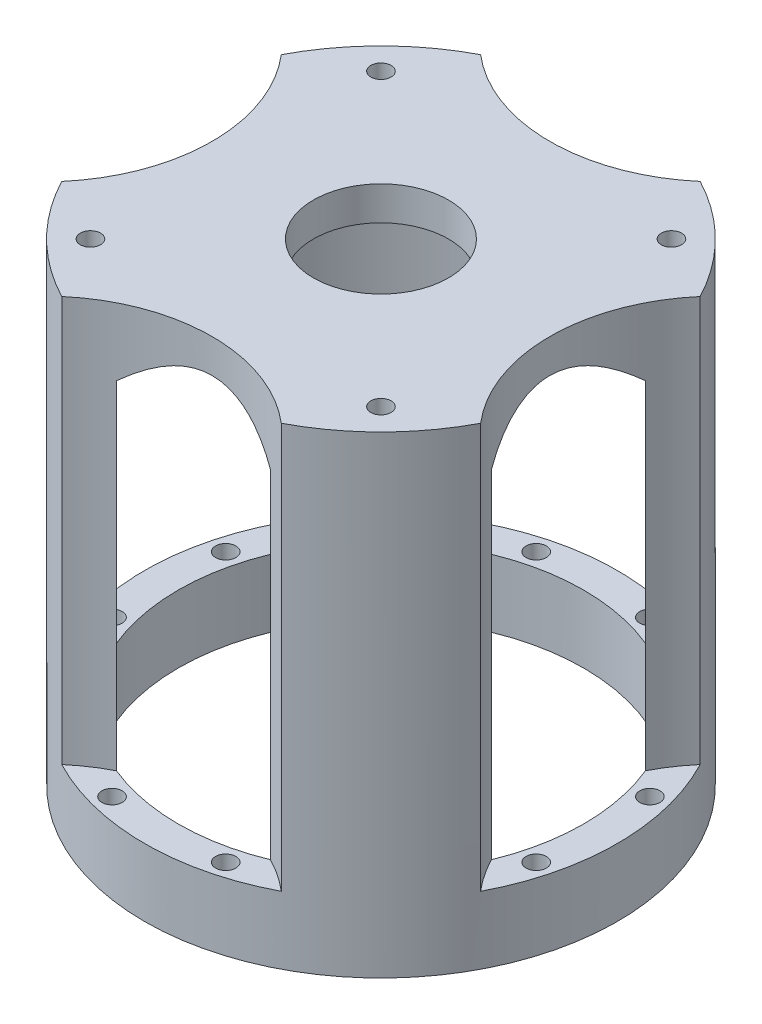
SolidWorks part; units mm, degrees
ref_plane "Front Plane" through (0, 0, 0) normal (0, 0, 1) x (1, 0, 0)
ref_plane "Top Plane" through (0, 0, 0) normal (0, 1, 0) x (1, 0, 0)
ref_plane "Right Plane" through (0, 0, 0) normal (1, 0, 0) x (0, 0, -1)
sketch "Sketch1" plane through (0, 0, 0) normal (0, 1, 0) x (1, 0, 0)
  line L0 (-8.4116, 31.3926) -> (0, 0) construction
  line L5 (-35, -35) -> (35, 35) construction
  line L6 (-35, 35) -> (35, -35) construction
  line L7 (0, 0) -> (8.6813, 0) construction
  circle A0 centre (0, 0) radius 35
  circle A1 centre (0, 0) radius 30
  circle A2 centre (0, 0) radius 32.5 construction
  circle A3 centre (-8.4116, 31.3926) radius 1.5
  circle A4 centre (8.4116, 31.3926) radius 1.5
  circle A6 centre (31.3926, 8.4116) radius 1.5
  circle A7 centre (31.3926, -8.4116) radius 1.5
  circle A9 centre (8.4116, -31.3926) radius 1.5
  circle A10 centre (-8.4116, -31.3926) radius 1.5
  circle A12 centre (-31.3926, -8.4116) radius 1.5
  circle A13 centre (-31.3926, 8.4116) radius 1.5
  circle A15 centre (22.981, -22.981) radius 1.5 [skipped]
  circle A16 centre (22.981, 22.981) radius 1.5 [skipped]
  circle A17 centre (-22.981, 22.981) radius 1.5 [skipped]
  circle A18 centre (-22.981, -22.981) radius 1.5 [skipped]
  point P35 (0, 0)
  dimension "D1" = 70
  dimension "D2" = 60
  dimension "D3" = 65
  dimension "D4" = 3
  dimension "D6" = 105
  dimension "D5" = 12
extrude "Boss-Extrude1" add sketch "Sketch1" along normal blind 65
sketch "Sketch2" plane through (0, 65, 0) normal (0, 1, 0) x (1, 0, 0)
  line L0 (-8.4116, 31.3926) -> (0, 0) construction
  line L7 (-21.5, -21.5) -> (21.5, -21.5) construction
  line L8 (-21.5, -21.5) -> (-21.5, 21.5) construction
  line L9 (-21.5, 21.5) -> (21.5, 21.5) construction
  line L10 (21.5, -21.5) -> (21.5, 21.5) construction
  line L11 (-21.5, -21.5) -> (21.5, 21.5) construction
  line L12 (-21.5, 21.5) -> (21.5, -21.5) construction
  line L13 (0, 0) -> (15.336, 0) construction
  circle A0 centre (0, 0) radius 32.5 construction
  circle A1 centre (-8.4116, 31.3926) radius 1.5
  circle A2 centre (8.4116, 31.3926) radius 1.5
  circle A4 centre (31.3926, 8.4116) radius 1.5
  circle A5 centre (31.3926, -8.4116) radius 1.5
  circle A7 centre (8.4116, -31.3926) radius 1.5
  circle A8 centre (-8.4116, -31.3926) radius 1.5
  circle A10 centre (-31.3926, -8.4116) radius 1.5
  circle A11 centre (-31.3926, 8.4116) radius 1.5
  circle A13 centre (0, 0) radius 10
  circle A14 centre (-21.5, 21.5) radius 1.5 construction
  circle A15 centre (21.5, 21.5) radius 1.5 construction
  circle A16 centre (21.5, -21.5) radius 1.5 construction
  circle A17 centre (-21.5, -21.5) radius 1.5 construction
  circle A18 centre (0, 0) radius 35
  circle A19 centre (-22.981, 22.981) radius 1.5 [skipped]
  circle A20 centre (22.981, 22.981) radius 1.5 [skipped]
  circle A21 centre (22.981, -22.981) radius 1.5 [skipped]
  circle A22 centre (-22.981, -22.981) radius 1.5 [skipped]
  point P0 (0, 0)
  point P37 (0, 0)
  dimension "D1" = 65
  dimension "D3" = 20
  dimension "D4" = 43
  dimension "D5" = 105
  dimension "D2" = 12
extrude "Boss-Extrude2" add sketch "Sketch2" along normal blind 5
sketch "Sketch3" plane through (0, 70, 0) normal (0, 1, 0) x (1, 0, 0)
  line L0 (0, 0) -> (0, 50) construction
  circle A0 centre (0, 50) radius 25
  dimension "D2" = 50
  dimension "D1" = 50
extrude "Cut-Extrude1" cut sketch "Sketch3" against normal blind 60
pattern_circular "CirPattern1" count 4 over 360 about axis through (0, 65, 0) along (0, -1, 0) of "Cut-Extrude1" reverse direction yes
chamfer "Chamfer1" distance 5 angle 45 4 edges at (-21.2132, 65, -21.2132) (21.2132, 65, -21.2132) (21.2132, 65, 21.2132) (-21.2132, 65, 21.2132)
sketch "Sketch4" plane through (0, 70, 0) normal (0, 1, 0) x (1, 0, 0)
  line L1 (21.5, -21.5) -> (21.5, 21.5) construction
  line L2 (21.5, 21.5) -> (-21.5, 21.5) construction
  line L3 (-21.5, 21.5) -> (-21.5, -21.5) construction
  line L4 (-21.5, -21.5) -> (21.5, -21.5) construction
  circle A0 centre (0, 0) radius 21.5 construction
  circle A1 centre (-21.5, 21.5) radius 1.5
  circle A2 centre (21.5, 21.5) radius 1.5
  circle A3 centre (21.5, -21.5) radius 1.5
  circle A4 centre (-21.5, -21.5) radius 1.5
  point P17 (0, 0)
  dimension "D2" = 3
  dimension "D1" = 43
  dimension "D3" = 4
extrude "Cut-Extrude2" cut sketch "Sketch4" against normal blind 4
